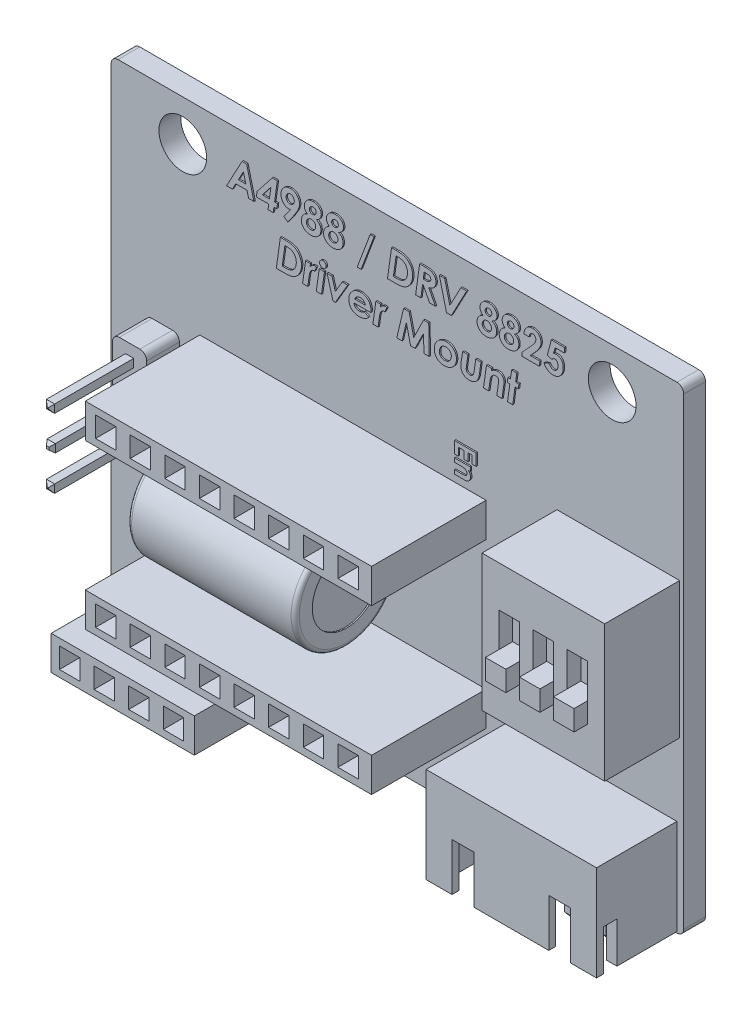
SolidWorks part; units mm, degrees
ref_plane "Front Plane" through (0, 0, 0) normal (0, 0, 1) x (1, 0, 0)
ref_plane "Top Plane" through (0, 0, 0) normal (0, 1, 0) x (1, 0, 0)
ref_plane "Right Plane" through (0, 0, 0) normal (1, 0, 0) x (0, 0, -1)
sketch "Sketch1" plane through (0, 0, 0) normal (0, 0, 1) x (1, 0, 0)
  line L1 (-21, 17.5) -> (21, 17.5)
  line L2 (-21, 17.5) -> (-21, -17.5)
  line L3 (-21, -17.5) -> (21, -17.5)
  line L4 (21, 17.5) -> (21, -17.5)
  line L5 (-21, 17.5) -> (21, -17.5) construction
  line L6 (-21, -17.5) -> (21, 17.5) construction
  point P0 (0, 0)
  dimension "D1" = 42
  dimension "D2" = 35
extrude "Boss-Extrude1" add sketch "Sketch1" along normal blind 1.6
sketch "Sketch2" plane through (0, 0, 1.6) normal (0, 0, 1) x (1, 0, 0)
  line L0 (21, 17.5) -> (-21, 17.5) construction
  circle A0 centre (-15.75, 14.5) radius 1.75
  circle A1 centre (15.75, 14.5) radius 1.75
  dimension "D5" = 3.5
  dimension "D6" = 3.5
  dimension "D1" = 31.5
  dimension "D2" = 3
  dimension "D3" = 3
  dimension "D4" = 15.75
extrude "Cut-Extrude1" cut sketch "Sketch2" against normal blind 1.6
sketch "Sketch3" plane through (0, 0, 1.6) normal (0, 0, 1) x (1, 0, 0)
  line L0 (21, 17.5) -> (-21, 17.5) construction
  line L1 (11.7, 5) -> (20.7, 5)
  line L2 (11.7, 5) -> (11.7, -5)
  line L3 (11.7, -5) -> (20.7, -5)
  line L4 (20.7, 5) -> (20.7, -5)
  line L5 (11.7, 5) -> (20.7, -5) construction
  line L6 (11.7, -5) -> (20.7, 5) construction
  line L7 (21, -17.5) -> (21, 17.5) construction
  point P0 (16.2, 0)
  dimension "D1" = 10
  dimension "D2" = 9
  dimension "D3" = 12.5
  dimension "D4" = 0.3
extrude "Boss-Extrude2" add sketch "Sketch3" along normal blind 5.5
sketch "Sketch4" plane through (0, 0, 7.1) normal (0, 0, 1) x (1, 0, 0)
  line L0 (16.2, -5) -> (16.2, 5) construction
  line L1 (11.7, -5) -> (20.7, -5) construction
  line L2 (20.7, 5) -> (11.7, 5) construction
  line L4 (15.45, 2) -> (16.95, 2)
  line L5 (15.45, 2) -> (15.45, -2)
  line L6 (15.45, -2) -> (16.95, -2)
  line L7 (16.95, 2) -> (16.95, -2)
  line L8 (15.45, 2) -> (16.95, -2) construction
  line L9 (15.45, -2) -> (16.95, 2) construction
  line L10 (17.95, 2) -> (19.45, 2)
  line L11 (17.95, 2) -> (17.95, -2)
  line L12 (17.95, -2) -> (19.45, -2)
  line L13 (19.45, 2) -> (19.45, -2)
  line L14 (14.45, 2) -> (12.95, 2)
  line L15 (14.45, 2) -> (14.45, -2)
  line L16 (14.45, -2) -> (12.95, -2)
  line L17 (12.95, 2) -> (12.95, -2)
  line L18 (12.95, -2) -> (14.45, -2)
  line L19 (12.95, -2) -> (12.95, -0.6674)
  line L21 (14.45, -2) -> (14.45, -0.6674)
  line L22 (15.45, -2) -> (16.95, -2)
  line L23 (15.45, -2) -> (15.45, -0.6674)
  line L25 (16.95, -2) -> (16.95, -0.6674)
  line L26 (17.95, -2) -> (19.45, -2)
  line L27 (17.95, -2) -> (17.95, -0.6674)
  line L29 (19.45, -2) -> (19.45, -0.6674)
  point P6 (16.2, 0)
  dimension "D1" = 4
  dimension "D2" = 4
  dimension "D3" = 4
  dimension "D4" = 0
  dimension "D5" = 0
  dimension "D6" = 1.5
  dimension "D7" = 1.5
  dimension "D8" = 1
  dimension "D9" = 1
  dimension "D10" = 1.5
extrude "Cut-Extrude3" cut sketch "Sketch4" against normal blind 1 contours L14 L17 L16 L15 | L7 L4 L5 L6 | L13 L10 L11 L12 region at (16.2, 0, 7.1) region at (18.7, 0, 7.1) region at (13.7, 0, 7.1)
sketch "Sketch5" plane through (0, 0, 7.1) normal (0, 0, 1) x (1, 0, 0)
  line L0 (14.45, 2) -> (14.45, -2) construction
  line L1 (12.95, -2) -> (14.45, -2)
  line L2 (12.95, -2) -> (12.95, -0.5101)
  line L3 (12.95, -0.5101) -> (14.45, -0.5101)
  line L4 (14.45, -2) -> (14.45, -0.5101)
  line L5 (15.45, -2) -> (16.95, -2) construction
  line L6 (15.45, -2) -> (16.95, -2)
  line L7 (15.45, -2) -> (15.45, -0.5101)
  line L8 (15.45, -0.5101) -> (16.95, -0.5101)
  line L9 (16.95, -2) -> (16.95, -0.5101)
  line L10 (16.95, 2) -> (16.95, -2) construction
  line L11 (15.45, 2) -> (15.45, -2) construction
  line L12 (17.95, -2) -> (19.45, -2)
  line L13 (17.95, -2) -> (17.95, -0.5101)
  line L14 (17.95, -0.5101) -> (19.45, -0.5101)
  line L15 (19.45, -2) -> (19.45, -0.5101)
  line L16 (19.45, 2) -> (19.45, -2) construction
  dimension "D1" = 1.5
  dimension "D2" = 0
  dimension "D3" = 0
extrude "Boss-Extrude3" add sketch "Sketch5" along normal blind 1 and the other way blind 1 separate body
sketch "Sketch6" plane through (0, 0, 1.6) normal (0, 0, 1) x (1, 0, 0)
  line L0 (-21, 17.5) -> (-21, -17.5) construction
  line L1 (-17, -13) -> (-6.5, -13)
  line L2 (-17, -13) -> (-17, -15.5)
  line L3 (-17, -15.5) -> (-6.5, -15.5)
  line L4 (-6.5, -13) -> (-6.5, -15.5)
  line L5 (-21, -17.5) -> (21, -17.5) construction
  dimension "D1" = 10.5
  dimension "D2" = 2.5
  dimension "D3" = 4
  dimension "D4" = 2
extrude "Boss-Extrude4" add sketch "Sketch6" along normal blind 8.4
sketch "Sketch7" plane through (0, 0, 10) normal (0, 0, 1) x (1, 0, 0)
  line L0 (-17, -13) -> (-17, -15.5) construction
  line L1 (-16.4, -13.5) -> (-14.9, -13.5)
  line L2 (-16.4, -13.5) -> (-16.4, -15)
  line L3 (-16.4, -15) -> (-14.9, -15)
  line L4 (-14.9, -13.5) -> (-14.9, -15)
  line L5 (-6.5, -13) -> (-17, -13) construction
  line L6 (-13.86, -13.5) -> (-13.86, -15)
  line L7 (-13.86, -13.5) -> (-12.36, -13.5)
  line L8 (-12.36, -13.5) -> (-12.36, -15)
  line L9 (-13.86, -15) -> (-12.36, -15)
  line L10 (-11.32, -13.5) -> (-11.32, -15)
  line L11 (-11.32, -13.5) -> (-9.82, -13.5)
  line L12 (-9.82, -13.5) -> (-9.82, -15)
  line L13 (-11.32, -15) -> (-9.82, -15)
  line L14 (-8.78, -13.5) -> (-8.78, -15)
  line L15 (-8.78, -13.5) -> (-7.28, -13.5)
  line L16 (-7.28, -13.5) -> (-7.28, -15)
  line L17 (-8.78, -15) -> (-7.28, -15)
  dimension "D1" = 1.5
  dimension "D2" = 1.5
  dimension "D3" = 0.6
  dimension "D4" = 0.5
  dimension "D5" = 4
extrude "Cut-Extrude4" cut sketch "Sketch7" against normal blind 8.4
sketch "Sketch8" plane through (0, 0, 1.6) normal (0, 0, 1) x (1, 0, 0)
  line L0 (-21, -17.5) -> (21, -17.5) construction
  line L1 (-14.5, 3) -> (6.5, 3)
  line L2 (-14.5, 3) -> (-14.5, 0.5)
  line L3 (-14.5, 0.5) -> (6.5, 0.5)
  line L4 (6.5, 3) -> (6.5, 0.5)
  line L5 (-14.5, -9) -> (6.5, -9)
  line L6 (-14.5, -9) -> (-14.5, -11.5)
  line L7 (-14.5, -11.5) -> (6.5, -11.5)
  line L8 (6.5, -9) -> (6.5, -11.5)
  line L9 (-21, 17.5) -> (-21, -17.5) construction
  dimension "D1" = 21
  dimension "D2" = 21
  dimension "D3" = 2.5
  dimension "D4" = 2.5
  dimension "D5" = 9.5
  dimension "D6" = 6
  dimension "D7" = 6.5
  dimension "D8" = 6.5
extrude "Boss-Extrude5" add sketch "Sketch8" along normal blind 8.4
sketch "Sketch9" plane through (0, 0, 10) normal (0, 0, 1) x (1, 0, 0)
  line L0 (-14.5, -9) -> (-14.5, -11.5) construction
  line L1 (-13.75, 2.5) -> (-12.25, 2.5)
  line L2 (-13.75, 2.5) -> (-13.75, 1)
  line L3 (-13.75, 1) -> (-12.25, 1)
  line L4 (-12.25, 2.5) -> (-12.25, 1)
  line L5 (-13.75, -9.5) -> (-12.25, -9.5)
  line L6 (-13.75, -9.5) -> (-13.75, -11)
  line L7 (-13.75, -11) -> (-12.25, -11)
  line L8 (-12.25, -9.5) -> (-12.25, -11)
  line L9 (6.5, -9) -> (-14.5, -9) construction
  line L10 (-14.5, 0.5) -> (6.5, 0.5) construction
  line L11 (-14.5, 3) -> (-14.5, 0.5) construction
  line L12 (-9.71, 2.5) -> (-9.71, 1)
  line L13 (-11.21, 2.5) -> (-9.71, 2.5)
  line L14 (-11.21, 2.5) -> (-11.21, 1)
  line L15 (-11.21, 1) -> (-9.71, 1)
  line L16 (-11.21, -9.5) -> (-9.71, -9.5)
  line L17 (-9.71, -9.5) -> (-9.71, -11)
  line L18 (-11.21, -9.5) -> (-11.21, -11)
  line L19 (-11.21, -11) -> (-9.71, -11)
  line L20 (-7.17, 2.5) -> (-7.17, 1)
  line L21 (-8.67, 2.5) -> (-7.17, 2.5)
  line L22 (-8.67, 2.5) -> (-8.67, 1)
  line L23 (-8.67, 1) -> (-7.17, 1)
  line L24 (-8.67, -9.5) -> (-7.17, -9.5)
  line L25 (-7.17, -9.5) -> (-7.17, -11)
  line L26 (-8.67, -9.5) -> (-8.67, -11)
  line L27 (-8.67, -11) -> (-7.17, -11)
  line L28 (-4.63, 2.5) -> (-4.63, 1)
  line L29 (-6.13, 2.5) -> (-4.63, 2.5)
  line L30 (-6.13, 2.5) -> (-6.13, 1)
  line L31 (-6.13, 1) -> (-4.63, 1)
  line L32 (-6.13, -9.5) -> (-4.63, -9.5)
  line L33 (-4.63, -9.5) -> (-4.63, -11)
  line L34 (-6.13, -9.5) -> (-6.13, -11)
  line L35 (-6.13, -11) -> (-4.63, -11)
  line L36 (-2.09, 2.5) -> (-2.09, 1)
  line L37 (-3.59, 2.5) -> (-2.09, 2.5)
  line L38 (-3.59, 2.5) -> (-3.59, 1)
  line L39 (-3.59, 1) -> (-2.09, 1)
  line L40 (-3.59, -9.5) -> (-2.09, -9.5)
  line L41 (-2.09, -9.5) -> (-2.09, -11)
  line L42 (-3.59, -9.5) -> (-3.59, -11)
  line L43 (-3.59, -11) -> (-2.09, -11)
  line L44 (0.45, 2.5) -> (0.45, 1)
  line L45 (-1.05, 2.5) -> (0.45, 2.5)
  line L46 (-1.05, 2.5) -> (-1.05, 1)
  line L47 (-1.05, 1) -> (0.45, 1)
  line L48 (-1.05, -9.5) -> (0.45, -9.5)
  line L49 (0.45, -9.5) -> (0.45, -11)
  line L50 (-1.05, -9.5) -> (-1.05, -11)
  line L51 (-1.05, -11) -> (0.45, -11)
  line L52 (2.99, 2.5) -> (2.99, 1)
  line L53 (1.49, 2.5) -> (2.99, 2.5)
  line L54 (1.49, 2.5) -> (1.49, 1)
  line L55 (1.49, 1) -> (2.99, 1)
  line L56 (1.49, -9.5) -> (2.99, -9.5)
  line L57 (2.99, -9.5) -> (2.99, -11)
  line L58 (1.49, -9.5) -> (1.49, -11)
  line L59 (1.49, -11) -> (2.99, -11)
  line L60 (5.53, 2.5) -> (5.53, 1)
  line L61 (4.03, 2.5) -> (5.53, 2.5)
  line L62 (4.03, 2.5) -> (4.03, 1)
  line L63 (4.03, 1) -> (5.53, 1)
  line L64 (4.03, -9.5) -> (5.53, -9.5)
  line L65 (5.53, -9.5) -> (5.53, -11)
  line L66 (4.03, -9.5) -> (4.03, -11)
  line L67 (4.03, -11) -> (5.53, -11)
  dimension "D1" = 1.5
  dimension "D2" = 1.5
  dimension "D3" = 1.5
  dimension "D4" = 1.5
  dimension "D5" = 0.75
  dimension "D6" = 0.5
  dimension "D7" = 0.5
  dimension "D8" = 0.75
  dimension "D9" = 8
extrude "Cut-Extrude5" cut sketch "Sketch9" against normal blind 8.4
sketch "Sketch10" plane through (0, 0, 1.6) normal (0, 0, 1) x (1, 0, 0)
  line L0 (-21, -17.5) -> (21, -17.5) construction
  line L1 (-18.5, 2.3) -> (-16, 2.3)
  line L2 (-18.5, 2.3) -> (-18.5, -5)
  line L3 (-18.5, -5) -> (-16, -5)
  line L4 (-16, 2.3) -> (-16, -5)
  line L5 (-21, 17.5) -> (-21, -17.5) construction
  dimension "D1" = 7.3
  dimension "D2" = 2.5
  dimension "D3" = 12.5
  dimension "D4" = 2.5
extrude "Boss-Extrude6" add sketch "Sketch10" along normal blind 2.4
sketch "Sketch11" plane through (0, 0, 4) normal (0, 0, 1) x (1, 0, 0)
  line L0 (-18.5, 2.3) -> (-18.5, -5) construction
  line L1 (-17.55, -1.05) -> (-16.95, -1.05)
  line L2 (-17.55, -1.05) -> (-17.55, -1.65)
  line L3 (-17.55, -1.65) -> (-16.95, -1.65)
  line L4 (-16.95, -1.05) -> (-16.95, -1.65)
  line L5 (-17.55, -1.05) -> (-16.95, -1.65) construction
  line L6 (-17.55, -1.65) -> (-16.95, -1.05) construction
  line L7 (-17.55, -3.59) -> (-16.95, -3.59)
  line L8 (-17.55, -3.59) -> (-17.55, -4.19)
  line L9 (-16.95, -3.59) -> (-16.95, -4.19)
  line L10 (-17.55, -4.19) -> (-16.95, -4.19)
  line L11 (-17.55, -1.05) -> (-16.95, -1.05)
  line L12 (-17.55, -1.05) -> (-17.55, -1.65)
  line L13 (-16.95, -1.05) -> (-16.95, -1.65)
  line L14 (-17.55, -1.65) -> (-16.95, -1.65)
  line L15 (-17.55, 1.49) -> (-16.95, 1.49)
  line L16 (-17.55, 1.49) -> (-17.55, 0.89)
  line L17 (-16.95, 1.49) -> (-16.95, 0.89)
  line L18 (-17.55, 0.89) -> (-16.95, 0.89)
  point P0 (-17.25, -1.35)
  dimension "D1" = 1.25
  dimension "D2" = 0.6
  dimension "D3" = 0.6
  dimension "D4" = 2
  dimension "D5" = 2
extrude "Boss-Extrude7" add sketch "Sketch11" along normal blind 6 contours L16 L18 L17 L15 | L4 L1 L2 L3 | L8 L10 L9 L7 region at (-17.25, -1.35, 4) region at (-17.25, -3.89, 4) region at (-17.25, 1.19, 4)
sketch "Sketch12" plane through (0, 0, 1.6) normal (0, 0, 1) x (1, 0, 0)
  line L0 (-21, -17.5) -> (21, -17.5) construction
  line L1 (8, -10.4) -> (20.5, -10.4)
  line L2 (8, -10.4) -> (8, -17.4)
  line L3 (8, -17.4) -> (20.5, -17.4)
  line L4 (20.5, -10.4) -> (20.5, -17.4)
  line L5 (21, -17.5) -> (21, 17.5) construction
  dimension "D1" = 12.5
  dimension "D2" = 7
  dimension "D3" = 0.1
  dimension "D4" = 0.5
extrude "Boss-Extrude9" add sketch "Sketch12" along normal blind 5.9
sketch "Sketch13" plane through (0, -17.4, 0) normal (0, -1, 0) x (1, 0, 0)
  line L0 (20.5, 7.5) -> (20.5, 1.6) construction
  line L1 (8.75, 7) -> (19.75, 7)
  line L2 (8.75, 7) -> (8.75, 2.1303)
  line L3 (8.75, 2.1303) -> (19.75, 2.1303)
  line L4 (19.75, 7) -> (19.75, 2.1303)
  line L5 (8.75, 7) -> (19.75, 2.1303) construction
  line L6 (8.75, 2.1303) -> (19.75, 7) construction
  line L7 (8, 7.5) -> (20.5, 7.5) construction
  point P0 (14.25, 4.5651)
  dimension "D1" = 11
  dimension "D2" = 0.75
  dimension "D3" = 0.5
extrude "Cut-Extrude6" cut sketch "Sketch13" against normal blind 5.9
sketch "Sketch14" plane through (0, -17.4, 0) normal (0, -1, 0) x (1, 0, 0)
  line L0 (8, 7.5) -> (8, 1.6) construction
  line L1 (8, 6) -> (20.5, 6)
  line L2 (8, 6) -> (8, 7)
  line L3 (8, 7) -> (20.5, 7)
  line L4 (20.5, 6) -> (20.5, 7)
  line L5 (20.5, 7.5) -> (20.5, 1.6) construction
  line L6 (19.75, 7) -> (8.75, 7) construction
  dimension "D1" = 0
  dimension "D2" = 1
extrude "Cut-Extrude7" cut sketch "Sketch14" against normal blind 3
sketch "Sketch15" plane through (0, 0, 7.5) normal (0, 0, 1) x (1, 0, 0)
  line L0 (8, -17.4) -> (20.5, -17.4) construction
  line L1 (9.9, -17.4) -> (11.5, -17.4)
  line L2 (9.9, -17.4) -> (9.9, -13.9)
  line L3 (9.9, -13.9) -> (11.5, -13.9)
  line L4 (11.5, -17.4) -> (11.5, -13.9)
  line L5 (8, -10.4) -> (8, -17.4) construction
  line L6 (17, -17.4) -> (18.6, -17.4)
  line L7 (17, -17.4) -> (17, -13.9)
  line L8 (17, -13.9) -> (18.6, -13.9)
  line L9 (18.6, -17.4) -> (18.6, -13.9)
  dimension "D1" = 1.6
  dimension "D2" = 1.6
  dimension "D3" = 5.5
  dimension "D4" = 1.9
  dimension "D5" = 3.5
extrude "Cut-Extrude8" cut sketch "Sketch15" against normal blind 3
sketch "Sketch16" plane through (0, 0, 0) normal (1, 0, 0) x (0, 0, -1)
  line L0 (-1.6, 17.5) -> (-1.6, -17.5) construction
  line L1 (-10, -9) -> (-1.6, -9) construction
  circle A0 centre (-5.35, -4) radius 3.75
  dimension "D1" = 7.5
  dimension "D2" = 3.75
  dimension "D3" = 5
extrude "Boss-Extrude10" add sketch "Sketch16" against normal blind 12.3 separate body
sketch "Sketch17" plane through (-12.3, 0, 0) normal (-1, 0, 0) x (0, 0, 1)
  circle A0 centre (5.35, -4) radius 2.5
  dimension "D1" = 5
extrude "Cut-Extrude9" cut sketch "Sketch17" against normal blind 0.1
sketch "Sketch18" plane through (0, 0, 0) normal (1, 0, 0) x (0, 0, -1)
  circle A0 centre (-5.35, -4) radius 2.5
  dimension "D1" = 5
extrude "Cut-Extrude10" cut sketch "Sketch18" against normal blind 0.1
fillet "Fillet1" radius 0.3 2 edges at (0, -4, 1.6) (-12.3, -4, 1.6)
fillet "Fillet2" radius 0.5 4 edges at (21, -17.5, 0.8) (21, 17.5, 0.8) (-21, 17.5, 0.8) (-21, -17.5, 0.8)
sketch "Sketch19" plane through (0, -11.5, 0) normal (0, -1, 0) x (1, 0, 0)
  line L0 (8.75, 7) -> (8.75, 2.1303) construction
  line L1 (10.19, 4.6303) -> (10.69, 4.6303)
  line L2 (10.19, 4.6303) -> (10.19, 4.1303)
  line L3 (10.19, 4.1303) -> (10.69, 4.1303)
  line L4 (10.69, 4.6303) -> (10.69, 4.1303)
  line L5 (12.73, 4.6303) -> (13.23, 4.6303)
  line L6 (13.23, 4.6303) -> (13.23, 4.1303)
  line L7 (12.73, 4.1303) -> (13.23, 4.1303)
  line L8 (12.73, 4.6303) -> (12.73, 4.1303)
  line L9 (15.27, 4.6303) -> (15.77, 4.6303)
  line L10 (15.77, 4.6303) -> (15.77, 4.1303)
  line L11 (15.27, 4.1303) -> (15.77, 4.1303)
  line L12 (15.27, 4.6303) -> (15.27, 4.1303)
  line L13 (17.81, 4.6303) -> (18.31, 4.6303)
  line L14 (18.31, 4.6303) -> (18.31, 4.1303)
  line L15 (17.81, 4.1303) -> (18.31, 4.1303)
  line L16 (17.81, 4.6303) -> (17.81, 4.1303)
  line L20 (8.75, 2.1303) -> (19.75, 2.1303) construction
  dimension "D1" = 0.5
  dimension "D2" = 0.5
  dimension "D3" = 1.44
  dimension "D5" = 2
  dimension "D4" = 4
extrude "Boss-Extrude11" add sketch "Sketch19" along normal blind 6
chamfer "Chamfer2" distance 0.2 angle 51 16 edges at (15.52, -17.5, 4.6303) (15.77, -17.5, 4.3803) (15.52, -17.5, 4.1303) (15.27, -17.5, 4.3803) (18.06, -17.5, 4.6303) (18.31, -17.5, 4.3803) (18.06, -17.5, 4.1303) (17.81, -17.5, 4.3803) (12.98, -17.5, 4.1303) (13.23, -17.5, 4.3803) (12.98, -17.5, 4.6303) (12.73, -17.5, 4.3803) (10.69, -17.5, 4.3803) (10.44, -17.5, 4.1303) (10.19, -17.5, 4.3803) (10.44, -17.5, 4.6303) first distance on face at (15.52, -17.5, 4.3803) first distance on face at (18.06, -17.5, 4.3803) first distance on face at (12.98, -17.5, 4.3803) first distance on face at (10.44, -17.5, 4.3803)
fillet "Fillet3" radius 0.5 4 edges at (-16, 2.3, 2.8) (-18.5, 2.3, 2.8) (-16, -5, 2.8) (-18.5, -5, 2.8)
chamfer "Chamfer3" distance 0.2 angle 51 12 edges at (-17.25, -3.59, 10) (-16.95, -3.89, 10) (-17.25, -4.19, 10) (-17.55, -3.89, 10) (-17.25, -1.65, 10) (-17.55, -1.35, 10) (-17.25, -1.05, 10) (-16.95, -1.35, 10) (-17.25, 1.49, 10) (-16.95, 1.19, 10) (-17.25, 0.89, 10) (-17.55, 1.19, 10) first distance on face at (-17.25, -3.59, 7) first distance on face at (-16.95, -3.89, 7) first distance on face at (-17.25, -4.19, 7) first distance on face at (-17.55, -3.89, 7) first distance on face at (-17.25, -1.35, 10) first distance on face at (-17.25, 1.49, 7) first distance on face at (-16.95, 1.19, 7) first distance on face at (-17.25, 0.89, 7) first distance on face at (-17.55, 1.19, 7)
sketch "Sketch20" plane through (0, 0, 1.6) normal (0, 0, 1) x (1, 0, 0)
  text T0 "A4988 / DRV 8825" font "Century Gothic" height in points 8
  text T1 "Driver Mount" font "Century Gothic" height in points 8
extrude "Boss-Extrude12" add sketch "Sketch20" along normal blind 0.1
sketch "Sketch21" plane through (0, 0, 1.6) normal (0, 0, 1) x (1, 0, 0)
  line L0 (4.2788, 3.4586) -> (4.2788, 8.7731) construction
  text T0 "En" font "Century Gothic" height in points 6
extrude "Boss-Extrude13" add sketch "Sketch21" along normal blind 0.1
